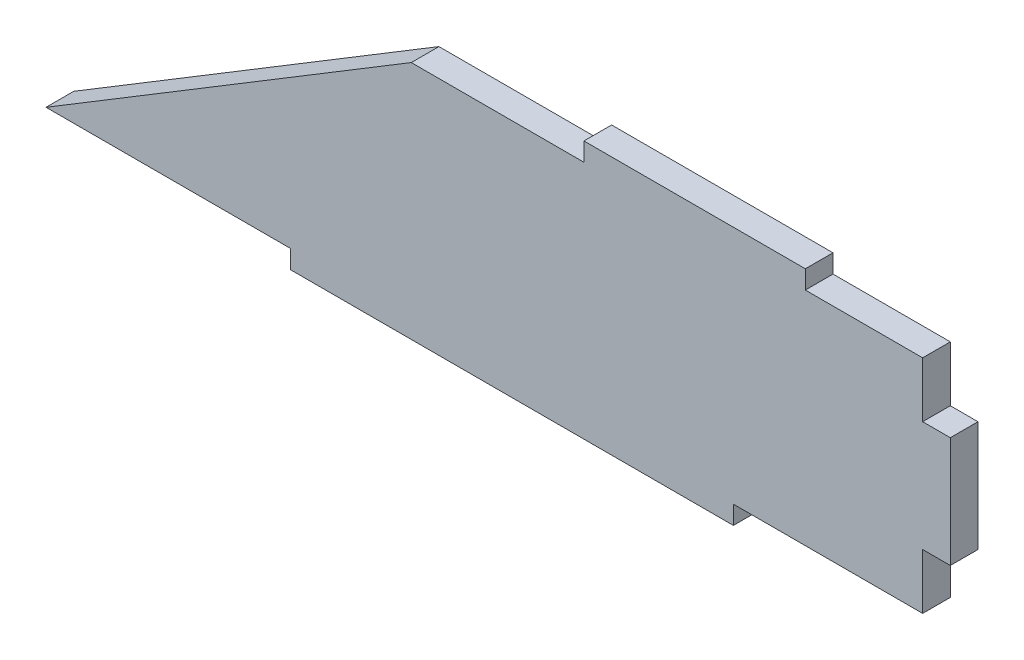
SolidWorks part; units mm, degrees
ref_plane "Front Plane" through (0, 0, 0) normal (0, 0, 1) x (1, 0, 0)
ref_plane "Top Plane" through (0, 0, 0) normal (0, 1, 0) x (1, 0, 0)
ref_plane "Right Plane" through (0, 0, 0) normal (1, 0, 0) x (0, 0, -1)
sketch "Sketch1" plane through (0, 0, 0) normal (0, 0, 1) x (1, 0, 0)
  line L0 (138.8804, 35.0708) -> (98.4944, 35.0708)
  line L1 (-162.8716, -41.1292) -> (-78.6706, -41.1292)
  line L4 (138.8804, -41.1292) -> (138.8804, -22.0792)
  line L5 (-162.8716, -41.1292) -> (138.8804, 35.0708) construction
  line L6 (-37.1416, 35.0708) -> (-162.8716, -41.1292)
  line L7 (-78.6706, -41.1292) -> (-78.6706, -47.4792)
  line L8 (-78.6706, -47.4792) -> (73.7294, -47.4792)
  line L9 (73.7294, -47.4792) -> (73.7294, -41.1292)
  line L10 (22.2944, 35.0708) -> (22.2944, 41.4208)
  line L11 (22.2944, 41.4208) -> (98.4944, 41.4208)
  line L12 (98.4944, 41.4208) -> (98.4944, 35.0708)
  line L15 (22.2944, 35.0708) -> (-37.1416, 35.0708)
  line L16 (73.7294, -41.1292) -> (138.8804, -41.1292)
  line L17 (138.8804, 16.0208) -> (148.4054, 16.0208)
  line L18 (138.8804, 16.0208) -> (138.8804, 35.0708)
  line L19 (148.4054, -22.0792) -> (138.8804, -22.0792)
  line L20 (148.4054, 16.0208) -> (148.4054, -22.0792) construction
  line L21 (148.4054, 16.0208) -> (148.4054, -22.0792)
  point P0 (0, 0)
  dimension "D2" = 301.752
  dimension "D3" = 76.2
  dimension "D4" = 6.35
  dimension "D5" = 152.4
  dimension "D6" = 6.35
  dimension "D7" = 76.2
  dimension "D8" = 40.386
  dimension "2.565" = 65.151
  dimension "D9" = 9.525
  dimension "D10" = 176.022
  dimension "D11" = 19.05
  dimension "D12" = 38.1
extrude "Boss-Extrude1" add sketch "Sketch1" along normal blind 9.525 contours L1 L7 L8 L9 L16 L4 L19 L21 L17 L18 L0 L12 L11 L10 L15 L6
